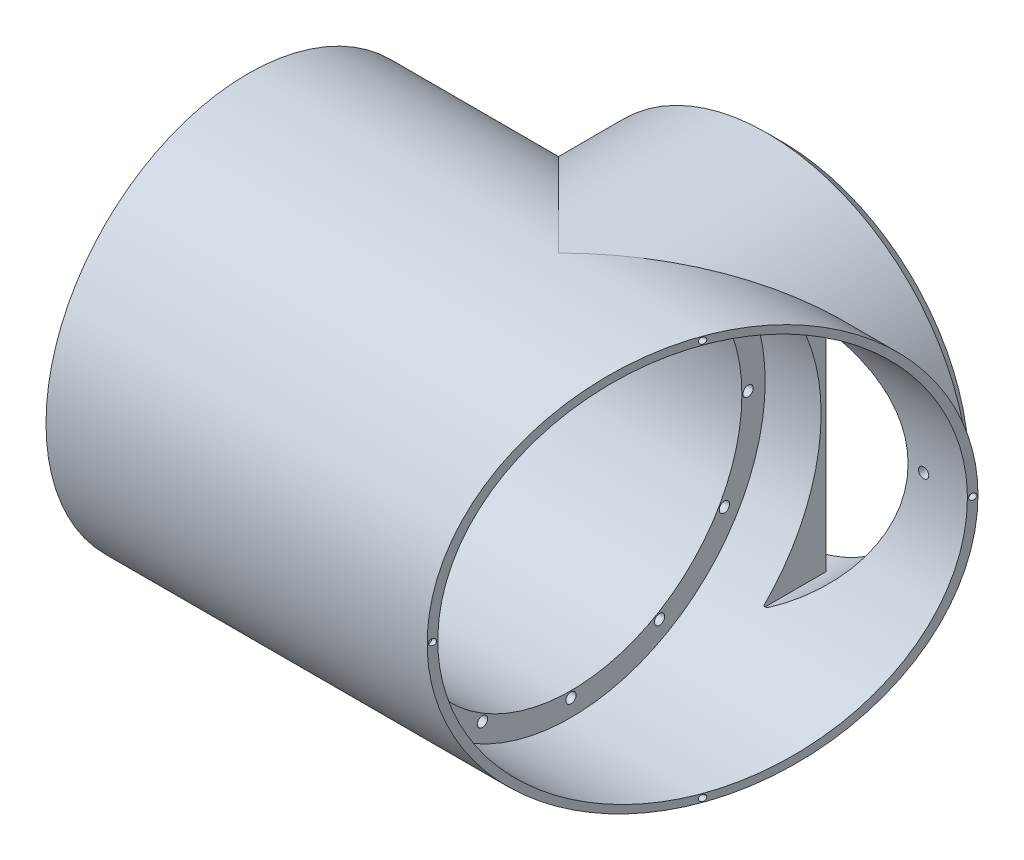
SolidWorks part; units mm, degrees
ref_plane "前视基准面" through (0, 0, 0) normal (0, 0, 1) x (1, 0, 0)
ref_plane "上视基准面" through (0, 0, 0) normal (0, 1, 0) x (1, 0, 0)
ref_plane "右视基准面" through (0, 0, 0) normal (1, 0, 0) x (0, 0, -1)
sketch "草图1" plane through (0, 0, 0) normal (0, 0, 1) x (1, 0, 0)
  circle A0 centre (0, 0) radius 65
  dimension "D1" = 130
extrude "凸台-拉伸1" add sketch "草图1" along normal blind 72
sketch "草图2" plane through (0, 0, 0) normal (1, 0, 0) x (0, 0, -1)
  line L0 (-72, 65) -> (-72, -65) construction
  circle A0 centre (-72, 0) radius 65
extrude "凸台-拉伸2" add sketch "草图2" along normal blind 70 and the other way blind 100 contours A0
sketch "草图3" plane through (70, 0, 0) normal (1, 0, 0) x (0, 0, -1)
  circle A0 centre (-72, 0) radius 45
  dimension "D1" = 90
extrude "切除-拉伸1" cut sketch "草图3" against normal through all
sketch "草图5" plane through (0, 0, 0) normal (0, 1, 0) x (1, 0, 0)
  line L0 (70, -7) -> (70, -137)
  line L1 (70, -137) -> (22.6839, -137)
  line L2 (-100, -137) -> (70, -137) construction
  line L3 (22.6839, -137) -> (70, -7)
  dimension "D1" = 20
extrude "切除-拉伸3" cut sketch "草图5" against normal through all and the other way through all
sketch "草图6" plane through (-100, 0, 0) normal (-1, 0, 0) x (0, 0, 1)
  circle A0 centre (72, 0) radius 57.5
  dimension "D1" = 115
extrude "切除-拉伸4" cut sketch "草图6" against normal blind 26
ref_plane "基准面1" through (75, 0, 0) normal (1, 0, 0) x (0, 0, -1)
sketch "草图7" plane through (75, 0, 0) normal (1, 0, 0) x (0, 0, -1)
  circle A0 centre (-72, 0) radius 62.5
  dimension "D1" = 125
extrude "切除-拉伸5" cut sketch "草图7" against normal offset from surface (71 mm away) 78 up to face at (-74, 0, 129.5)
sketch "草图8" plane through (4, 0, 0) normal (1, 0, 0) x (0, 0, -1)
  circle A0 centre (-72, 0) radius 55
  dimension "D1" = 110
extrude "切除-拉伸6" cut sketch "草图8" against normal offset from surface (62 mm away) 16 up to face at (-74, 0, 129.5)
hole_wizard "M4 螺纹孔1" positions "草图10" profile "草图9" tap size "M4" standard "GB"
sketch "草图10" plane through (-74, 0, 0) normal (-1, 0, 0) x (0, 0, 1)
  line L0 (72, 0) -> (72, 70.2146) construction
  circle A0 centre (72, 0) radius 51 construction
  point P0 (72, 51)
  dimension "D1" = 102
sketch "草图9" plane through (-74, 51, 72) normal (0, 1, 0) x (0, 0, 1)
  line L0 (0, 0) -> (0, 11.0914)
  line L1 (0, 11.0914) -> (1.65, 10.1)
  line L2 (1.65, 10.1) -> (1.65, 0)
  line L5 (1.65, 0) -> (0, 0)
  line L10 (0, 11.0914) -> (-1.65, 10.1) construction
  line L11 (0, -6.35) -> (0, 107.95) construction
  dimension "螺纹孔钻头直径" = 3.3
  dimension "螺纹孔钻头深度" = 10.1
  dimension "导头角度" = 118
cosmetic thread "孔螺蚊线1" parameters "D1"=8, "D2"=4
ref_axis "基准轴1" through (-74, 0, 72) along (1, 0, 0)
pattern_circular "阵列(圆周)1" count 12 over 360 about axis through (-74, 0, 72) along (1, 0, 0) of "M4 螺纹孔1"
hole_wizard "M4 螺纹孔2" positions "草图12" profile "草图11" tap size "M4" standard "GB"
sketch "草图12" plane through (4, 0, 0) normal (1, 0, 0) x (0, 0, -1)
  line L0 (-72, 0) -> (-178.0941, 0) construction
  circle A0 centre (-72, 0) radius 57 construction
  point P0 (-129, 0)
  dimension "D1" = 114
sketch "草图11" plane through (4, 0, 129) normal (0, 1, 0) x (0, 0, -1)
  line L0 (0, 0) -> (0, 11.0914)
  line L1 (0, 11.0914) -> (1.65, 10.1)
  line L2 (1.65, 10.1) -> (1.65, 0)
  line L5 (1.65, 0) -> (0, 0)
  line L10 (0, 11.0914) -> (-1.65, 10.1) construction
  line L11 (0, -6.35) -> (0, 107.95) construction
  dimension "螺纹孔钻头直径" = 3.3
  dimension "螺纹孔钻头深度" = 10.1
  dimension "导头角度" = 118
cosmetic thread "孔螺蚊线2" parameters "D1"=8, "D2"=4
pattern_circular "阵列(圆周)2" count 12 over 360 about axis through (-74, 0, 72) along (1, 0, 0) of "M4 螺纹孔2"
ref_plane "基准面4" through (75, 0, 0) normal (1, 0, 0) x (0, 0, -1)
sketch "草图18" plane through (75, 0, 0) normal (1, 0, 0) x (0, 0, -1)
  line L0 (-72, 0) -> (-72, 69.6517) construction
  line L1 (-72, 0) -> (-72, -78.4145) construction
  circle A0 centre (-72, 0) radius 63.75 construction
  circle A1 centre (-72, 63.75) radius 1
  circle A2 centre (-72, -63.75) radius 1
  dimension "D1" = 127.5
  dimension "D2" = 2
  dimension "D3" = 2
extrude "切除-拉伸17" cut sketch "草图18" against normal blind 32 contours A1 | A2
sketch "草图19" plane through (75, 0, 0) normal (1, 0, 0) x (0, 0, -1)
  line L0 (-72, 0) -> (-150.5345, 0) construction
  circle A0 centre (-72, 0) radius 63.75 construction
  circle A1 centre (-135.75, 0) radius 1
  dimension "D1" = 127.5
  dimension "D2" = 2
extrude "切除-拉伸18" cut sketch "草图19" against normal blind 53
sketch "草图20" plane through (75, 0, 0) normal (1, 0, 0) x (0, 0, -1)
  line L0 (-72, 0) -> (25.4168, 0) construction
  circle A0 centre (-72, 0) radius 63.75 construction
  circle A1 centre (-8.25, 0) radius 1
  dimension "D1" = 127.5
  dimension "D2" = 2
extrude "切除-拉伸19" cut sketch "草图20" against normal blind 7
ref_axis "基准轴2" through (0, 0, 72) along (0, 0, -1)
chamfer "倒角3" distance 5 angle 45 1 edges at (65, 0, 0)
hole_wizard "M4 螺纹孔4" positions "草图28" profile "草图27" tap size "M4" standard "GB"
sketch "草图28" plane through (0, 0, 0) normal (0, 0, -1) x (-1, 0, 0)
  line L1 (0, 0) -> (-90.0957, 0) construction
  circle A0 centre (0, 0) radius 55 construction
  point P0 (-55, 0)
  dimension "D1" = 110
sketch "草图27" plane through (55, 0, 0) normal (1, 0, 0) x (0, 1, 0)
  line L0 (0, 0) -> (0, 11.0914)
  line L1 (0, 11.0914) -> (1.65, 10.1)
  line L2 (1.65, 10.1) -> (1.65, 0)
  line L5 (1.65, 0) -> (0, 0)
  line L10 (0, 11.0914) -> (-1.65, 10.1) construction
  line L11 (0, -6.35) -> (0, 107.95) construction
  dimension "螺纹孔钻头直径" = 3.3
  dimension "螺纹孔钻头深度" = 10.1
  dimension "导头角度" = 118
cosmetic thread "孔螺蚊线4" parameters "D1"=8, "D2"=4
sketch "草图29" plane through (0, 0, 0) normal (0, 0, -1) x (-1, 0, 0)
  circle A0 centre (0, 0) radius 50
  dimension "D1" = 100
extrude "切除-拉伸23" cut sketch "草图29" against normal blind 8
pattern_circular "阵列(圆周)3" count 10 over 360 about axis through (0, 0, 72) along (0, 0, -1) of "M4 螺纹孔4"
sketch "草图30" plane through (0, 0, 8) normal (0, 0, -1) x (-1, 0, 0)
  line L0 (0, 0) -> (-115.0931, 0) construction
  line L1 (-22, 44.8999) -> (-22, -44.8999)
  arc A0 (-22, 44.8999) -> (-22, -44.8999) centre (0, 0) ccw
  dimension "D1" = 100
  dimension "D2" = 22
extrude "切除-拉伸24" cut sketch "草图30" against normal blind 20
